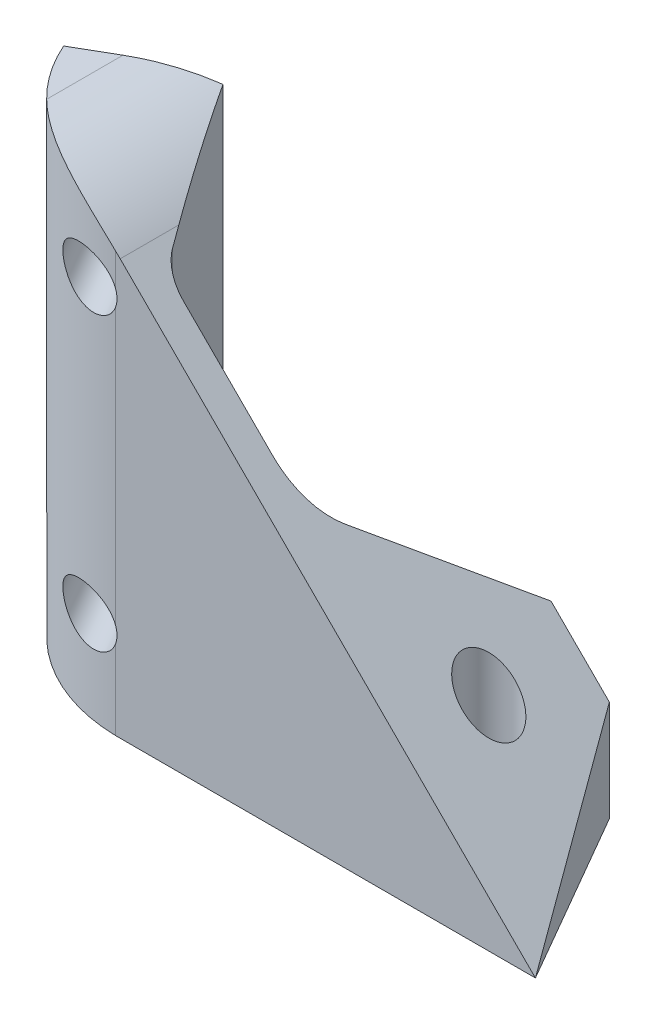
SolidWorks part; units mm, degrees
other "Markup1"
sketch "Sketch26" plane through (25.6218, 0, -129.9038) normal (-0.1134, -0.9932, -0.0259) x (0.9576, -0.1162, 0.2636)
ref_plane "Front Plane" through (0, 0, 0) normal (0, 0, 1) x (1, 0, 0)
ref_plane "Top Plane" through (0, 0, 0) normal (0, 1, 0) x (1, 0, 0)
ref_plane "Right Plane" through (0, 0, 0) normal (1, 0, 0) x (0, 0, -1)
sketch "Sketch1" plane through (0, 0, 0) normal (0, 1, 0) x (1, 0, 0)
  line L0 (0, 0) -> (150, 0)
  line L1 (0, 0) -> (75, 129.9038)
  line L2 (75, 129.9038) -> (150, 0)
  dimension "D1" = 60
  dimension "D2" = 150
  dimension "D3" = 60
sketch "Sketch2" plane through (0, 0, 0) normal (0, 1, 0) x (1, 0, 0)
  line L1 (74, 5) -> (174, 5) construction
  line L2 (74, 5) -> (74, 25) construction
  line L3 (74, 25) -> (174, 25) construction
  line L4 (174, 5) -> (174, 25) construction
  line L5 (41.3301, 61.5859) -> (91.3301, 148.1884) construction
  line L6 (91.3301, 148.1884) -> (108.6506, 138.1884) construction
  line L7 (108.6506, 138.1884) -> (58.6506, 51.5859) construction
  line L8 (58.6506, 51.5859) -> (41.3301, 61.5859) construction
  line L9 (0, 0) -> (150, 0) construction
  line L10 (108.6506, 138.1884) -> (58.6506, 51.5859)
  line L11 (58.6506, 51.5859) -> (41.3301, 61.5859)
  line L12 (41.3301, 61.5859) -> (91.3301, 148.1884)
  line L13 (91.3301, 148.1884) -> (108.6506, 138.1884)
  line L14 (74, 25) -> (174, 25)
  line L15 (174, 5) -> (174, 25)
  line L16 (74, 5) -> (174, 5)
  line L17 (74, 5) -> (74, 25)
  line L18 (0, 0) -> (75, 129.9038) construction
  dimension "D1" = 20
  dimension "D2" = 5
  dimension "D3" = 74
  dimension "D4" = 20
  dimension "D5" = 74
  dimension "D6" = 5
  dimension "D7" = 100
  dimension "D8" = 100
  dimension "D9" = 0
  dimension "D10" = 0
sketch "Sketch4" plane through (0, 0, 0) normal (0, 1, 0) x (1, 0, 0)
  line L5 (41.1191, 35.292) -> (0, 0) construction
  line L6 (0, 0) -> (53.0061, 91.8093) construction
  line L7 (68.4402, 27.9736) -> (51.1204, 17.9723) construction
  line L8 (68.4402, 27.9736) -> (58.4388, 45.2934) construction
  line L9 (58.4388, 45.2934) -> (41.1191, 35.292) construction
  line L10 (51.1204, 17.9723) -> (41.1191, 35.292) construction
  line L11 (68.4402, 27.9736) -> (41.1191, 35.292) construction
  line L12 (58.4388, 45.2934) -> (51.1204, 17.9723) construction
  line L13 (58.4388, 45.2934) -> (41.1191, 35.292)
  line L15 (0, 0) -> (131.24, 0) construction
  line L17 (51.1204, 17.9723) -> (41.1191, 35.292)
  line L18 (68.4402, 27.9736) -> (51.1204, 17.9723)
  line L19 (68.4402, 27.9736) -> (58.4388, 45.2934)
  line L20 (51.1204, 17.9723) -> (0, 0) construction
  point P0 (54.7796, 31.6328)
  dimension "D1" = 20
  dimension "D2" = 20
  dimension "D3" = 21.269
  dimension "D4" = 0
  dimension "D5" = 54.1877
  dimension "D6" = 60
  dimension "D7" = 19.37
ref_plane "Plane1" through (4.3301, 0, 2.5) normal (0.866, 0, 0.5) x (0.5, 0, -0.866)
ref_plane "Plane2" through (21.6506, 0, 12.5) normal (-0.866, 0, -0.5) x (-0.5, 0, 0.866)
ref_plane "Plane3" through (0, 0, -25) normal (0, 0, 1) x (1, 0, 0)
ref_plane "Plane4" through (0, 0, -5) normal (0, 0, 1) x (1, 0, 0)
ref_plane "Plane6" through (-5.0007, 0, -8.6599) normal (-0.5001, 0, -0.866) x (-0.866, 0, 0.5001)
ref_plane "Plane7" through (5.0007, 0, 8.6599) normal (-0.5001, 0, -0.866) x (-0.866, 0, 0.5001)
sketch "Sketch28" plane through (5.0007, 0, 8.6599) normal (-0.5001, 0, -0.866) x (-0.866, 0, 0.5001)
  line L1 (-73.2569, 0) -> (-53.2569, 0)
  line L2 (-73.2569, 0) -> (-73.2569, 80)
  line L3 (-73.2569, 80) -> (-53.2569, 80)
  line L4 (-53.2569, 0) -> (-53.2569, 80)
  dimension "D1" = 80
sketch "Sketch30" plane through (0, 0, 0) normal (0, 1, 0) x (1, 0, 0)
  line L0 (74, 5) -> (174, 5) construction
  line L1 (74, 25) -> (154, 25)
  line L2 (74, 25) -> (74, 5)
  line L3 (74, 5) -> (154, 5)
  line L4 (154, 25) -> (154, 5)
  dimension "D1" = 80
sketch "Sketch31" plane through (0, 0, 0) normal (0, 1, 0) x (1, 0, 0)
  line L10 (78, 0) -> (150, 0)
  line L14 (105.1743, 5) -> (84.5929, 5)
  line L15 (80.263, 7.4997) -> (68.4402, 27.9736)
  line L16 (68.4402, 27.9736) -> (51.1204, 17.9723)
  line L17 (68.4402, 27.9736) -> (58.4388, 45.2934) construction
  line L20 (122.6795, 30) -> (132.6795, 30)
  line L21 (132.6795, 30) -> (150, 0)
  line L22 (122.6795, 30) -> (105.1743, 5)
  line L26 (75, 129.9038) -> (150, 0) construction
  line L27 (74, 25) -> (174, 25) construction
  line L28 (0, 0) -> (150, 0) construction
  arc A2 (84.5929, 5) -> (80.263, 7.4997) centre (84.5929, 10) cw
  arc A5 (51.1204, 17.9723) -> (78, 0) centre (78.6065, 29.9939) ccw
  point P2 (84.5929, 39.1872)
  dimension "D1" = 5
  dimension "D2" = 5
  dimension "D7" = 30
  dimension "D3" = 125
  dimension "D4" = 10
  dimension "D5" = 72
  dimension "D6" = 5
extrude "Boss-Extrude1" add sketch "Sketch31" along normal blind 80
sketch "Sketch32" plane through (0, 0, 0) normal (0, 0, 1) x (1, 0, 0)
  line L0 (70, 80) -> (150, 0)
  line L1 (150, 0) -> (150, 80)
  line L2 (150, 80) -> (70, 80)
  dimension "D1" = 45
extrude "Cut-Extrude1" cut sketch "Sketch32" against normal blind 60
sketch "Sketch33" plane through (0, 0, 0) normal (0, 0, 1) x (1, 0, 0)
  line L0 (51.1204, 25) -> (76.1204, 0)
  line L1 (51.1204, 0) -> (51.1204, 80) construction
  line L2 (75, 0) -> (150, 0) construction
  line L3 (76.1204, 0) -> (51.1204, 0)
  line L4 (51.1204, 0) -> (51.1204, 25)
  line L5 (51.1204, 0) -> (0, 0) construction
  line L6 (0, 0) -> (150, 0) construction
  dimension "D1" = 25
  dimension "D2" = 25
extrude "Cut-Extrude2" [suppressed] cut sketch "Sketch33" against normal through all both and the other way through all
fillet "Fillet1" radius 30 1 edges at (70, 80, -13.2637)
fillet "Fillet2" [suppressed] radius 10
fillet "Fillet3" radius 10 1 edges at (105.1743, 22.4128, -5)
sketch "Sketch34" plane through (5.0007, 0, 8.6599) normal (-0.5001, 0, -0.866) x (-0.866, 0, 0.5001)
  line L0 (-60.7087, 80) -> (-53.2569, 80) construction
  line L1 (-73.2569, 0) -> (-53.2569, 0) construction
  line L2 (-63.2569, 0) -> (-63.2569, 79.9187) construction
  circle A0 centre (-63.2569, 15) radius 2.3
  circle A1 centre (-63.2569, 65) radius 2.3
  ellipse E0 centre (-60.7087, 50) end of major axis (-95.3513, 50) minor radius 30 (-60.7087, 80) -> (-73.2569, 77.9628) ccw construction
  dimension "D1" = 4.6
  dimension "D2" = 15
  dimension "D3" = 15
extrude "Cut-Extrude3" cut sketch "Sketch34" against normal through all both and the other way through all
ref_plane "Plane8" through (7.001, 0, 12.1238) normal (-0.5001, 0, -0.866) x (-0.866, 0, 0.5001)
sketch "Sketch35" plane through (7.001, 0, 12.1238) normal (-0.5001, 0, -0.866) x (-0.866, 0, 0.5001)
  circle A0 centre (-63.2569, 65) radius 4.5
  circle A1 centre (-63.2569, 15) radius 4.5
  dimension "D1" = 9
extrude "Cut-Extrude4" cut sketch "Sketch35" against normal through all
sketch "Sketch36" plane through (0, 0, 0) normal (0, -1, 0) x (1, 0, 0)
  line L0 (78, 0) -> (150, 0) construction
  circle A0 centre (127, -15) radius 2.3
  dimension "D3" = 4.6
  dimension "D1" = 15
  dimension "D2" = 23
extrude "Cut-Extrude5" cut sketch "Sketch36" against normal through all
ref_plane "Plane9" through (0, 4, 0) normal (0, -1, 0) x (-1, 0, 0)
sketch "Sketch37" plane through (0, 4, 0) normal (0, -1, 0) x (-1, 0, 0)
  circle A0 centre (-127, 15) radius 4.5
  dimension "D1" = 9
extrude "Cut-Extrude6" cut sketch "Sketch37" against normal through all
mirror "Mirror1" [suppressed] about plane through (0, 0, 0) normal (0, 0, 1) of bodies 151
delete or keep bodies "Body-Delete/Keep 1" [suppressed] type delete bodies bodies 151
